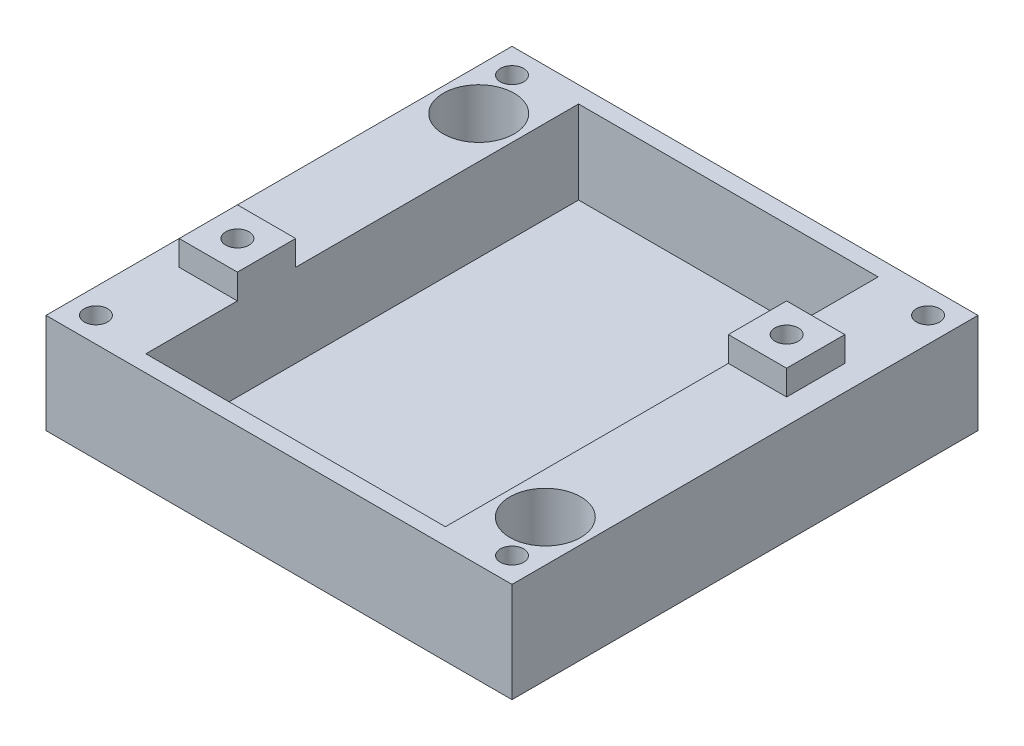
SolidWorks part; units mm, degrees
ref_plane "Спереди" through (0, 0, 0) normal (0, 0, 1) x (1, 0, 0)
ref_plane "Сверху" through (0, 0, 0) normal (0, 1, 0) x (1, 0, 0)
ref_plane "Справа" through (0, 0, 0) normal (1, 0, 0) x (0, 0, -1)
sketch "Эскиз1" plane through (0, 0, 0) normal (0, 1, 0) x (1, 0, 0)
  line L1 (28, -28) -> (-28, -28)
  line L2 (28, -28) -> (28, 28)
  line L3 (28, 28) -> (-28, 28)
  line L4 (-28, -28) -> (-28, 28)
  line L5 (28, -28) -> (-28, 28) construction
  line L6 (28, 28) -> (-28, -28) construction
  point P0 (0, 0)
  dimension "D1" = 56
  dimension "D2" = 56
extrude "Бобышка-Вытянуть1" add sketch "Эскиз1" along normal blind 12
sketch "Эскиз2" plane through (0, 12, 0) normal (0, 1, 0) x (1, 0, 0)
  line L1 (-18, 26) -> (18, 26)
  line L2 (-18, 26) -> (-18, -26)
  line L3 (-18, -26) -> (18, -26)
  line L4 (18, 26) -> (18, -26)
  line L5 (-18, 26) -> (18, -26) construction
  line L6 (-18, -26) -> (18, 26) construction
  point P0 (0, 0)
  dimension "D1" = 36
  dimension "D2" = 52
extrude "Вырез-Вытянуть1" cut sketch "Эскиз2" against normal blind 10
sketch "Эскиз4" plane through (0, 12, 0) normal (0, 1, 0) x (1, 0, 0)
  line L1 (-25, -8) -> (-18, -8)
  line L2 (-25, -8) -> (-25, -15)
  line L3 (-25, -15) -> (-18, -15)
  line L4 (-18, -8) -> (-18, -15)
  line L5 (-25, -8) -> (-18, -15) construction
  line L6 (-25, -15) -> (-18, -8) construction
  line L11 (18, 15) -> (25, 15)
  line L12 (18, 15) -> (18, 8)
  line L13 (18, 8) -> (25, 8)
  line L14 (25, 15) -> (25, 8)
  line L15 (18, 15) -> (25, 8) construction
  line L16 (18, 8) -> (25, 15) construction
  point P0 (-21.5, -11.5)
  point P5 (21.5, 11.5)
  dimension "D1" = 21.5
  dimension "D2" = 11.5
  dimension "D3" = 7
  dimension "D4" = 7
  dimension "D5" = 21.5
  dimension "D6" = 11.5
  dimension "D7" = 7
  dimension "D8" = 7
extrude "Бобышка-Вытянуть3" add sketch "Эскиз4" along normal blind 3
sketch "Эскиз5" plane through (0, 15, 0) normal (0, 1, 0) x (1, 0, 0)
  circle A0 centre (-21.5, -11.5) radius 1.4
  circle A1 centre (21.5, 11.5) radius 1.4
  dimension "D1" = 2.8
  dimension "D2" = 2.8
  dimension "D3" = 11.5
  dimension "D4" = 11.5
  dimension "D5" = 21.5
  dimension "D6" = 21.5
extrude "Вырез-Вытянуть3" cut sketch "Эскиз5" against normal blind 8
sketch "Эскиз6" plane through (0, 12, 0) normal (0, 1, 0) x (1, 0, 0)
  circle A0 centre (-23, 19) radius 2.25
  circle A1 centre (23, -19) radius 2.25
  dimension "D2" = 4.5
  dimension "D6" = 4.5
  dimension "D1" = 23
  dimension "D3" = 19
  dimension "D4" = 19
  dimension "D5" = 23
extrude "Вырез-Вытянуть4" cut sketch "Эскиз6" against normal through all
sketch "Эскиз7" plane through (0, 12, 0) normal (0, 1, 0) x (1, 0, 0)
  circle A0 centre (-23, 19) radius 4.25
  circle A1 centre (23, -19) radius 4.25
  dimension "D1" = 8.5
  dimension "D2" = 8.5
extrude "Вырез-Вытянуть5" cut sketch "Эскиз7" against normal blind 9
chamfer "Фаска1" distance 1.5 distance2 2 2 edges at (23, 3, 21.25) (-23, 3, -16.75) first distance on face at (23, 0, 21.25) first distance on face at (-23, 0, -16.75)
sketch "Эскиз8" plane through (0, 12, 0) normal (0, 1, 0) x (1, 0, 0)
  line L0 (28, 28) -> (-28, 28) construction
  line L1 (-28, 28) -> (-28, -28) construction
  line L2 (-28, -28) -> (28, -28) construction
  line L3 (28, -28) -> (28, 28) construction
  circle A0 centre (-25, 25) radius 1.4
  circle A1 centre (25, -25) radius 1.4
  circle A2 centre (-25, -25) radius 1.4
  circle A3 centre (25, 25) radius 1.4
  dimension "D3" = 2.8
  dimension "D6" = 2.8
  dimension "D9" = 2.8
  dimension "D12" = 2.8
  dimension "D1" = 3
  dimension "D2" = 3
  dimension "D4" = 3
  dimension "D5" = 3
  dimension "D7" = 3
  dimension "D8" = 3
  dimension "D10" = 3
  dimension "D11" = 3
extrude "Вырез-Вытянуть6" cut sketch "Эскиз8" against normal blind 8
